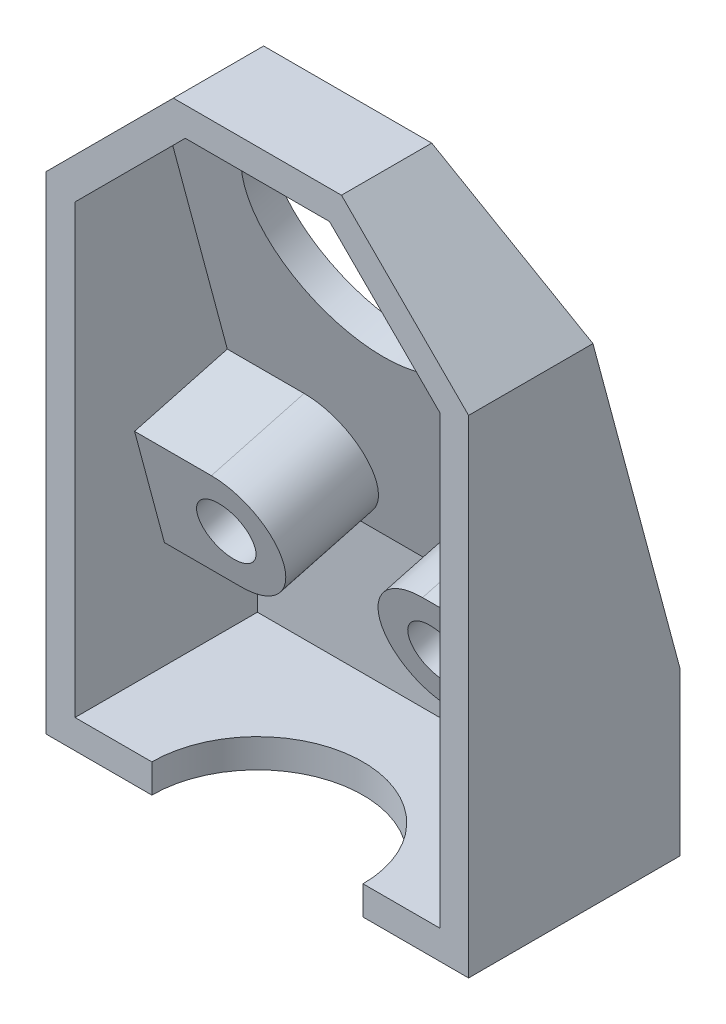
SolidWorks part; units mm, degrees
material "ABS"
ref_plane "前视基准面" through (0, 0, 0) normal (0, 0, 1) x (1, 0, 0)
ref_plane "上视基准面" through (0, 0, 0) normal (0, 1, 0) x (1, 0, 0)
ref_plane "右视基准面" through (0, 0, 0) normal (1, 0, 0) x (0, 0, -1)
other "Configuration Table"
sketch "草图1" plane through (0, 0, 0) normal (0, 0, 1) x (1, 0, 0)
  line L0 (173.4776, -15.3198) -> (148.4776, -15.3198)
  line L1 (148.4776, -15.3198) -> (148.4776, 12.1802)
  line L2 (148.4776, 12.1802) -> (155.9776, 19.6802)
  line L3 (165.9776, 19.6802) -> (173.4776, 12.1802)
  line L4 (173.4776, 12.1802) -> (173.4776, -15.3198)
  line L5 (165.9776, 19.6802) -> (155.9776, 19.6802)
  line L6 (160.9776, -15.3198) -> (160.9776, 19.6802) construction
  dimension "D1" = 25
  dimension "D2" = 35
  dimension "D3" = 10
  dimension "D4" = 27.5
extrude "凸台-拉伸1" add sketch "草图1" along normal blind 20 contours L1 L2 L5 L3 L4 L0
chamfer "倒角1" distance 8 angle 25 5 edges at (148.4776, -1.5698, 20) (152.2276, 15.9302, 20) (160.9776, 19.6802, 20) (169.7276, 15.9302, 20) (173.4776, -1.5698, 20) first distance on face at (148.4776, -1.5698, 10) first distance on face at (152.2276, 15.9302, 10) first distance on face at (160.9776, 19.6802, 10) first distance on face at (169.7276, 15.9302, 10) first distance on face at (173.4776, -1.5698, 10)
chamfer "倒角2" distance 5 angle 20 1 edges at (160.9776, -15.3198, 20) first distance on face at (160.9776, 3.755, 20)
sketch "草图6" plane through (173.4776, 0, 0) normal (1, 0, 0) x (0, 0, -1)
  line L0 (0, -5.3198) -> (-6.6987, 19.6802)
  line L1 (0, 12.1802) -> (0, -15.3198) construction
  line L2 (-12, 19.6802) -> (0, 19.6802) construction
  line L3 (-6.6987, 19.6802) -> (0, 19.6802)
  line L4 (0, 19.6802) -> (0, -5.3198)
  line L6 (-12, -15.3198) -> (0, -15.3198) construction
  dimension "D1" = 10
  dimension "D2" = 15
extrude "切除-拉伸3" cut sketch "草图6" against normal through all
ref_plane "基准面1" through (0, -5.6913, 21.2402) normal (0, 0.2588, -0.9659) x (-1, 0, 0)
sketch "草图5" plane through (0, -4.0612, 21.677) normal (0, -0.2588, 0.9659) x (1, 0, 0)
  line L0 (155.4776, -3.5721) -> (166.4776, -3.5721) construction
  line L4 (155.4776, -0.5721) -> (148.4776, -0.5721)
  line L5 (148.4776, -13.3796) -> (148.4776, 13.1834) construction
  line L6 (148.4776, -0.5721) -> (148.4776, -6.5721)
  line L7 (148.4776, -6.5721) -> (155.4776, -6.5721)
  line L8 (166.4776, -6.5721) -> (173.4776, -6.5721)
  line L9 (173.4776, 13.1834) -> (173.4776, -13.3796) construction
  line L10 (173.4776, -6.5721) -> (173.4776, -0.5721)
  line L11 (166.4776, -0.5721) -> (173.4776, -0.5721)
  line L12 (160.9776, 20.4279) -> (160.9776, -16.4854) construction
  line L13 (155.9776, 20.4279) -> (165.9776, 20.4279) construction
  line L14 (173.4776, -16.4854) -> (148.4776, -16.4854) construction
  circle A0 centre (155.4776, -3.5721) radius 3
  circle A1 centre (166.4776, -3.5721) radius 3
  circle A2 centre (155.4776, -3.5721) radius 1.55 construction
  circle A3 centre (166.4776, -3.5721) radius 1.55 construction
  circle A4 centre (160.9776, -3.5721) radius 3 construction
  dimension "D1" = 6
  dimension "D2" = 3.1
  dimension "D3" = 11
  dimension "D4" = 24
extrude "切除-拉伸2" cut sketch "草图5" against normal blind 3 contours A1 | L8 A1 L10 | A0 | L4 A0 L7 L6 region at (150.8477, -7.5116, 20.7524) region at (155.4776, -7.5116, 20.7524) region at (171.1074, -7.5116, 20.7524) region at (166.4776, -7.5116, 20.7524)
sketch "草图7" plane through (0, -4.9148, 18.3424) normal (0, -0.2588, 0.9659) x (1, 0, 0)
  circle A0 centre (166.4776, -1.8845) radius 1.5
  circle A1 centre (155.4776, -1.8845) radius 1.5
  dimension "D1" = 3
extrude "切除-拉伸4" cut sketch "草图7" against normal through all
sketch "草图18" plane through (0, 0, 0) normal (0, 0, -1) x (-1, 0, 0)
  line L36 (-148.4776, -5.3198) -> (-173.4776, -5.3198) construction
  line L37 (-173.8185, -31.4588) -> (-148.1366, -31.4588)
  line L38 (-173.8185, -31.4588) -> (-173.8185, 20.8192)
  line L39 (-173.8185, 20.8192) -> (-148.1366, 20.8192)
  line L40 (-148.1366, -31.4588) -> (-148.1366, 20.8192)
  line L41 (-173.8185, -31.4588) -> (-148.1366, 20.8192) construction
  line L42 (-173.8185, 20.8192) -> (-148.1366, -31.4588) construction
  line L44 (-171.9776, 11.5589) -> (-171.9776, -5.3198)
  line L45 (-165.3562, 18.1802) -> (-171.9776, 11.5589)
  line L46 (-156.5989, 18.1802) -> (-165.3562, 18.1802)
  line L47 (-149.9776, 11.5589) -> (-156.5989, 18.1802)
  line L48 (-149.9776, -5.3198) -> (-149.9776, 11.5589)
  line L49 (-149.9776, -13.8198) -> (-149.9776, -5.3198)
  line L50 (-171.9776, -13.8198) -> (-149.9776, -13.8198)
  line L51 (-171.9776, -5.3198) -> (-171.9776, -13.8198)
  line L52 (-171.9776, 11.5589) -> (-171.9776, -5.3198)
  line L53 (-165.3562, 18.1802) -> (-171.9776, 11.5589)
  line L54 (-156.5989, 18.1802) -> (-165.3562, 18.1802)
  line L55 (-149.9776, 11.5589) -> (-156.5989, 18.1802)
  line L56 (-149.9776, -5.3198) -> (-149.9776, 11.5589)
  line L57 (-149.9776, -13.8198) -> (-149.9776, -5.3198)
  line L58 (-171.9776, -13.8198) -> (-149.9776, -13.8198)
  line L59 (-171.9776, -5.3198) -> (-171.9776, -13.8198)
  point P0 (-160.9776, -5.3198)
  dimension "D1" = 1.5
extrude "切除-拉伸6" cut sketch "草图18" against normal through all
sketch "草图19" plane through (0, -13.8198, 0) normal (0, -1, 0) x (1, 0, 0)
  line L0 (160.9776, 0) -> (160.9776, 20) construction
  line L1 (171.9776, 0) -> (149.9776, 0) construction
  line L2 (156.2179, 20) -> (165.7372, 20) construction
  line L3 (155.4776, 11) -> (148.4349, 11)
  line L4 (148.4349, 11) -> (148.4349, 24.5627)
  line L5 (148.4349, 24.5627) -> (173.5203, 24.5627)
  line L6 (173.5203, 24.5627) -> (173.5203, 11)
  line L7 (173.5203, 11) -> (166.4776, 11)
  line L8 (155.4776, 11) -> (166.4776, 11)
  circle A0 centre (160.9776, 11) radius 5.5 construction
  line M4 (170.3411, 18.7261) -> (151.614, 18.7261)
  line M5 (151.614, 18.7261) -> (149.9776, 15.2168)
  line M6 (149.9776, 15.2168) -> (149.9776, 0)
  line M8 (171.9776, 0) -> (171.9776, 15.2168)
  line M9 (171.9776, 15.2168) -> (170.3411, 18.7261)
  dimension "D1" = 11
  dimension "D2" = 11
extrude "切除-拉伸7" cut sketch "草图19" against normal through all contours A0 L0 | L0 A0 | L7 L6 L5 L4 L3 M6 M5 M4 M9 M8 | L3 L8 L7 M8 M9 M4 M5 M6 region at (160.9776, -13.8198, 14.7689) region at (160.9776, -13.8198, 20.5925)
sketch "草图20" plane through (0, -13.8198, 0) normal (0, -1, 0) x (1, 0, 0)
  line L0 (171.9776, 11) -> (149.9776, 11) construction
  circle A0 centre (160.9776, 11) radius 5.5
  dimension "D1" = 11
extrude "切除-拉伸8" cut sketch "草图20" against normal blind 5
shell "抽壳3" thickness 1.5 removed face at (166.4776, -3.6256, 0.454) removed face at (160.9776, -1.344, 11) removed face at (155.4776, -3.6256, 0.454) removed face at (160.9776, -11.3198, 8.25) removed face at (160.9776, -8.8198, 8.25)
sketch "草图21" plane through (0, -0.7446, 2.7788) normal (0, -0.2588, 0.9659) x (1, 0, 0)
  line L0 (155.4776, 1.1155) -> (151.4776, 1.1155)
  line L1 (151.4776, -9.053) -> (151.4776, 13.4119) construction
  line L2 (151.4776, 1.1155) -> (151.4776, -4.8845)
  line L4 (151.4776, -4.8845) -> (155.4776, -4.8845)
  line L5 (166.4776, 1.1155) -> (170.4776, 1.1155)
  line L6 (170.4776, -4.941) -> (170.4776, 12.0943) construction
  line L7 (170.4776, 1.1155) -> (170.4776, -4.8845)
  line L8 (170.4776, 13.4119) -> (170.4776, -9.053) construction
  line L9 (170.4776, -4.8845) -> (166.4776, -4.8845)
  circle A0 centre (166.4776, -1.8845) radius 1.5 construction
  circle A1 centre (155.4776, -1.8845) radius 1.5 construction
  circle A2 centre (166.4776, -1.8845) radius 1.5
  circle A3 centre (155.4776, -1.8845) radius 1.5
  circle A4 centre (155.4776, -1.8845) radius 3
  circle A5 centre (166.4776, -1.8845) radius 3
  circle M4 centre (155.4776, -1.8845) radius 1.5
  circle M5 centre (166.4776, -1.8845) radius 1.5
  line M6 (151.4776, 12.0943) -> (151.4776, -4.941)
  line M8 (170.4776, -4.941) -> (170.4776, 12.0943)
  dimension "D1" = 1.5
extrude "凸台-拉伸2" add sketch "草图21" along normal blind 5 contours A4 L0 L4 M6 | A4 M4 | A5 L9 L5 M8 | A5 M5 region at (152.4358, -2.5649, 2.2911) region at (157.5389, -0.5738, 2.8246) region at (169.5193, -2.5649, 2.2911) region at (168.5389, -0.5738, 2.8246)
sketch "草图22" plane through (0, -0.7446, 2.7788) normal (0, -0.2588, 0.9659) x (1, 0, 0)
  line L0 (160.9776, 18.0395) -> (160.9776, -4.941) construction
  line L1 (164.7349, 18.0395) -> (157.2202, 18.0395) construction
  line L2 (151.4776, -4.941) -> (170.4776, -4.941) construction
  circle A0 centre (160.9776, 12.1155) radius 5.75
  circle A2 centre (166.4776, -1.8845) radius 1.5 construction
  dimension "D1" = 11.5
  dimension "D2" = 14
extrude "切除-拉伸9" cut sketch "草图22" against normal blind 10
